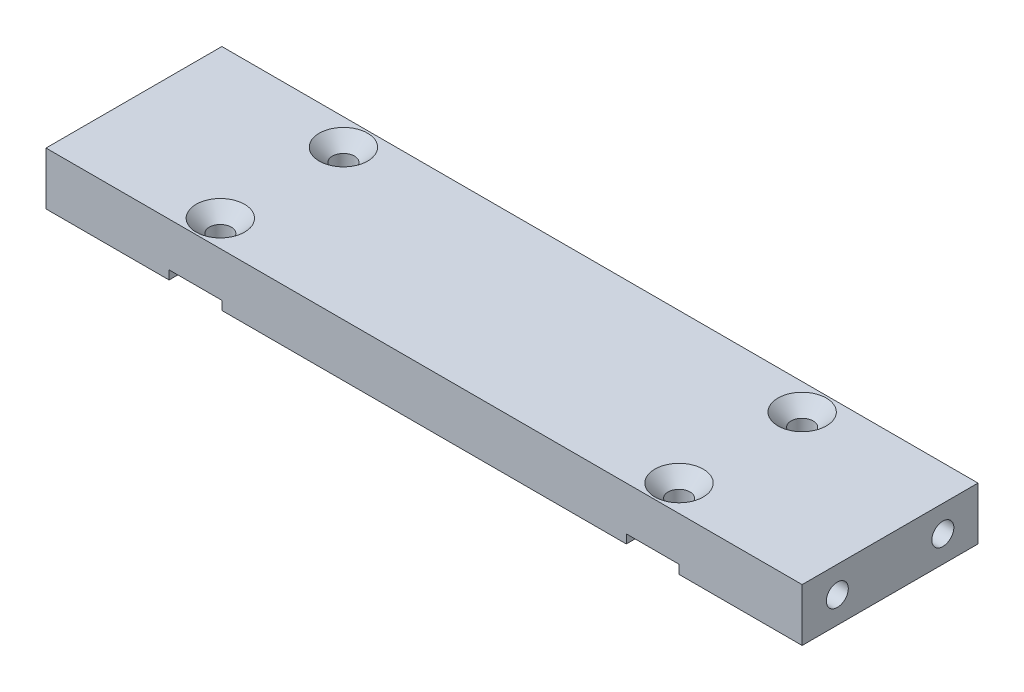
SolidWorks part; units mm, degrees
material "1060 Alloy"
ref_plane "Front Plane" through (0, 0, 0) normal (0, 0, 1) x (1, 0, 0)
ref_plane "Top Plane" through (0, 0, 0) normal (0, 1, 0) x (1, 0, 0)
ref_plane "Right Plane" through (0, 0, 0) normal (1, 0, 0) x (0, 0, -1)
sketch "Sketch2" plane through (0, 0, 0) normal (0, 1, 0) x (1, 0, 0)
  line L1 (86, -20) -> (0, -20)
  line L5 (0, -20) -> (0, 0)
  line L6 (86, -20) -> (86, 0)
  line L11 (86, 0) -> (0, 0)
  dimension "D2" = 86
  dimension "D9" = 20
extrude "Boss-Extrude1" add sketch "Sketch2" along normal blind 6
hole_wizard "Tap Drill for M3 Tap2" positions "Sketch6" profile "Sketch5" hole size "M3" standard "ISO"
sketch "Sketch6" plane through (86, 0.7792, 7.6405) normal (1, 0, 0) x (0, 0, -1)
  line L4 (-12.3595, -0.7792) -> (7.6405, -0.7792) construction
  line L6 (-12.3595, 5.2208) -> (-12.3595, -0.7792) construction
  line L7 (7.6405, 5.2208) -> (7.6405, -0.7792) construction
  point P0 (-8.3595, 2.2208)
  point P2 (3.6405, 2.2208)
  dimension "D1" = 3
  dimension "D2" = 4
  dimension "D3" = 4
sketch "Sketch5" plane through (86, 3, 16) normal (0, 1, 0) x (0, 0, -1)
  line L0 (0, 0) -> (0, 8.7511)
  line L1 (0, 8.7511) -> (1.25, 8)
  line L2 (1.25, 8) -> (1.25, 0)
  line L5 (1.25, 0) -> (0, 0)
  line L10 (0, 8.7511) -> (-1.25, 8) construction
  line L11 (0, -6.35) -> (0, 107.95) construction
  dimension "Hole Dia." = 2.5
  dimension "Hole Depth" = 8
  dimension "Drill Angle" = 118
hole_wizard "Tap Drill for M3 Tap1" positions "Sketch4" profile "Sketch3" hole size "M3" standard "ISO"
sketch "Sketch4" plane through (0, 0, 0) normal (-1, 0, 0) x (0, 0, 1)
  line L0 (0, 0) -> (20, 0) construction
  line L2 (0, 6) -> (0, 0) construction
  line L3 (20, 6) -> (20, 0) construction
  point P0 (4, 3)
  point P2 (16, 3)
  dimension "D1" = 3
  dimension "D2" = 4
  dimension "D3" = 4
sketch "Sketch3" plane through (0, 3, 4) normal (0, 1, 0) x (0, 0, 1)
  line L0 (0, 0) -> (0, 8.7511)
  line L1 (0, 8.7511) -> (1.25, 8)
  line L2 (1.25, 8) -> (1.25, 0)
  line L5 (1.25, 0) -> (0, 0)
  line L10 (0, 8.7511) -> (-1.25, 8) construction
  line L11 (0, -6.35) -> (0, 107.95) construction
  dimension "Hole Dia." = 2.5
  dimension "Hole Depth" = 8
  dimension "Drill Angle" = 118
sketch "Sketch7" plane through (0, 0, 0) normal (0, -1, 0) x (1, 0, 0)
  line L0 (0, 20) -> (86, 20) construction
  line L1 (14, 20) -> (20, 20)
  line L2 (14, 20) -> (14, 0)
  line L3 (14, 0) -> (20, 0)
  line L4 (20, 20) -> (20, 0)
  line L5 (86, 0) -> (0, 0) construction
  line L6 (0, 0) -> (0, 20) construction
  line L7 (72, 20) -> (66, 20)
  line L8 (72, 20) -> (72, 0)
  line L9 (72, 0) -> (66, 0)
  line L10 (66, 20) -> (66, 0)
  line L11 (86, 20) -> (86, 0) construction
  dimension "D1" = 14
  dimension "D2" = 6
  dimension "D3" = 14
extrude "Cut-Extrude1" cut sketch "Sketch7" against normal blind 1
hole_wizard "Tap Drill for M3x0.5 Tap1" positions "3DSketch1" profile "Sketch8" hole size "M3x0.5" standard "ANSI Metric" end condition up to next
sketch3d "3DSketch1"
  line L0 (72, 1, 0) -> (72, 1, 20) construction
  line L1 (66, 1, 0) -> (72, 1, 0) construction
  line L2 (20, 1, 20) -> (14, 1, 20) construction
  line L3 (14, 0, 20) -> (14, 0, 0) construction
  point P0 (16.8284, 1, 17)
  point P2 (16.8284, 1, 3)
  point P4 (69, 1, 17)
  point P6 (69, 1, 3)
  point P13 (0, 0, 0)
  dimension "D1" = 3
  dimension "D2" = 3
  dimension "D3" = 3
  dimension "D4" = 3
sketch "Sketch8" plane through (16.8284, 1, 17) normal (1, 0, 0) x (0, 0, -1)
  line L0 (0, 0) -> (0, 5)
  line L1 (0, 5) -> (1.25, 5)
  line L2 (1.25, 5) -> (1.25, 0)
  line L5 (1.25, 0) -> (0, 0)
  line L11 (0, -6.35) -> (0, 107.95) construction
  dimension "Thru Hole Dia." = 2.5
  dimension "Thru Hole Depth" = 5
chamfer "Chamfer1" distance 1.5 angle 45 4 edges at (16.8284, 6, 15.75) (16.8284, 6, 1.75) (69, 6, 15.75) (69, 6, 1.75)
